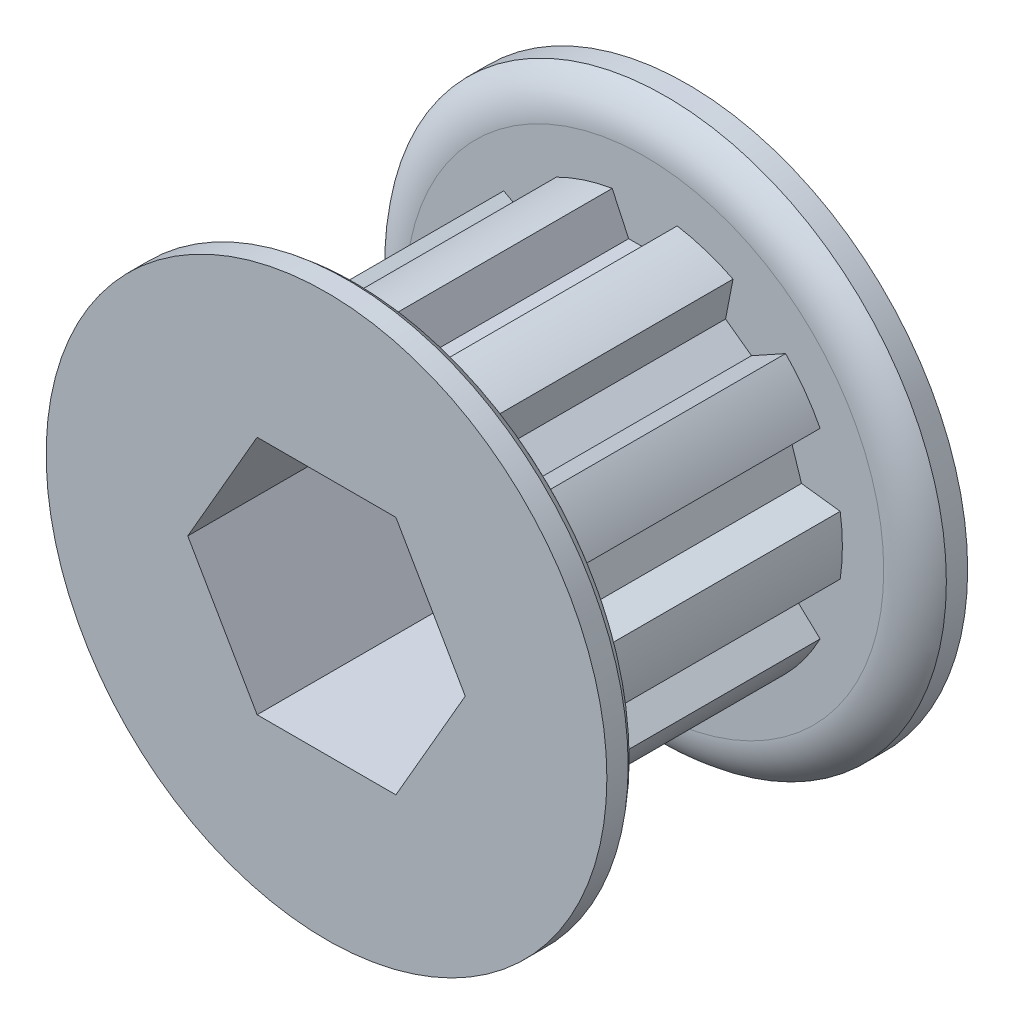
SolidWorks part; units mm, degrees
ref_plane "Front Plane" through (0, 0, 0) normal (0, 0, 1) x (1, 0, 0)
ref_plane "Top Plane" through (0, 0, 0) normal (0, 1, 0) x (1, 0, 0)
ref_plane "Right Plane" through (0, 0, 0) normal (1, 0, 0) x (0, 0, -1)
sketch "Sketch1" plane through (0, 0, 0) normal (0, 0, 1) x (1, 0, 0)
  line L0 (-1.2878, 7.7293) -> (-0.635, 6.3293)
  line L1 (-0.635, 6.3293) -> (0.635, 6.3293)
  line L2 (0.635, 6.3293) -> (1.2878, 7.7293)
  line L3 (-1.2878, 7.7293) -> (1.2878, 7.7293)
  line L4 (0, 0) -> (0, 6.3293) construction
  line L5 (0, 6.3293) -> (0, 8.6153) construction
  circle A0 centre (0, 0) radius 8.0899 construction
  circle A1 centre (0, 0) radius 11.1125 construction
  circle A2 centre (0, 0) radius 7.8359 construction
  point P6 (0, 7.7293)
  point P11 (0, 8.0899)
  point P13 (0, 11.1125)
  point P14 (0, 7.8359)
  dimension "D1" = 1.4
  dimension "PD" = 16.1798
  dimension "OD" = 22.225
  dimension "D3" = 1.27
  dimension "Gear OD" = 15.6718
  dimension "b" = 50
  dimension "hs" = 2.286
sketch "Sketch2" plane through (0, 0, 0) normal (1, 0, 0) x (0, 0, -1)
  line L0 (-3.9878, 2.5) -> (10.3124, 2.5)
  line L4 (-3.9878, 11.1125) -> (-2.2987, 11.1125) construction
  line L5 (-2.2987, 11.1125) -> (-2.2987, 7.8359) construction
  line L6 (-2.2987, 7.8359) -> (8.6233, 7.8359)
  line L7 (8.6233, 7.8359) -> (8.6233, 11.1125) construction
  line L8 (8.6233, 11.1125) -> (10.3124, 11.1125) construction
  line L9 (10.3124, 11.1125) -> (10.3124, 2.5)
  line L10 (-10.3124, 0) -> (10.3124, 0) construction
  line L11 (-3.9878, 2.5) -> (-3.9878, 11.1125)
  line L13 (-3.9878, 11.1125) -> (-3.1432, 11.1125)
  line L14 (-2.2987, 9.4742) -> (-2.2987, 7.8359)
  line L15 (8.6233, 7.8359) -> (8.6233, 9.4742)
  line L16 (9.4679, 11.1125) -> (10.3124, 11.1125)
  arc A0 (-2.2987, 9.4742) -> (-3.1432, 11.1125) centre (-4.31, 9.4742) ccw
  arc A1 (8.6233, 9.4742) -> (9.4679, 11.1125) centre (10.6346, 9.4742) cw
  point P12 (-2.2987, 9.4742)
  point P14 (-3.1432, 11.1125)
  point P20 (8.6233, 9.4742)
  point P21 (9.4679, 11.1125)
  point P25 (8.6233, 0)
  point P26 (-2.2987, 0)
  dimension "D1" = 14.3002
  dimension "OA" = 20.6248
  dimension "Bore" = 5
  dimension "Inside Width" = 10.922
revolve "Revolve1" add sketch "Sketch2" angle 360 mid plane about L10
sketch "Sketch3" plane through (0, 0, 0) normal (0, 0, 1) x (1, 0, 0)
  line L0 (-0.635, 6.3293) -> (0.635, 6.3293) construction
  line L1 (0.635, 6.3293) -> (1.2878, 7.7293) construction
  line L2 (-1.2878, 7.7293) -> (-0.635, 6.3293) construction
  line L3 (-0.635, 6.3293) -> (0.635, 6.3293)
  line L4 (0.635, 6.3293) -> (1.2878, 7.7293)
  line L5 (-1.2878, 7.7293) -> (-0.635, 6.3293)
  circle A0 centre (0, 0) radius 7.8359 construction
  arc A1 (1.2878, 7.7293) -> (-1.2878, 7.7293) centre (0, 0) ccw
extrude "Cut-Extrude1" cut sketch "Sketch3" against normal up to vertex (8.6233 mm away) from vertex up to point (0, 7.8359, -8.6233) starting at point (0, 7.8359, 2.2987)
fillet "Fillet1" [suppressed] radius 0.61
pattern_circular "CirPattern1" count 10 over 360 about axis through (0, 0, 10.3124) along (0, 0, 1) of "Cut-Extrude1", "Fillet1"
ref_plane "Contact Plane 2" through (0, 0, -10.3124) normal (0, 0, -1) x (-1, 0, 0)
ref_axis "Center Axis 1" through (0, 0, -10.3124) along (0, 0, 1)
sketch "Sketch6" plane through (0, 0, -10.3124) normal (0, 0, -1) x (-1, 0, 0)
  line L1 (5.4993, 0) -> (2.7496, 4.7625)
  line L2 (2.7496, 4.7625) -> (-2.7496, 4.7625)
  line L3 (-2.7496, 4.7625) -> (-5.4993, 0)
  line L4 (-5.4993, 0) -> (-2.7496, -4.7625)
  line L5 (-2.7496, -4.7625) -> (2.7496, -4.7625)
  line L6 (2.7496, -4.7625) -> (5.4993, 0)
  circle A0 centre (0, 0) radius 4.7625 construction
  dimension "D1" = 9.525
extrude "Cut-Extrude2" cut sketch "Sketch6" against normal blind 25.654
